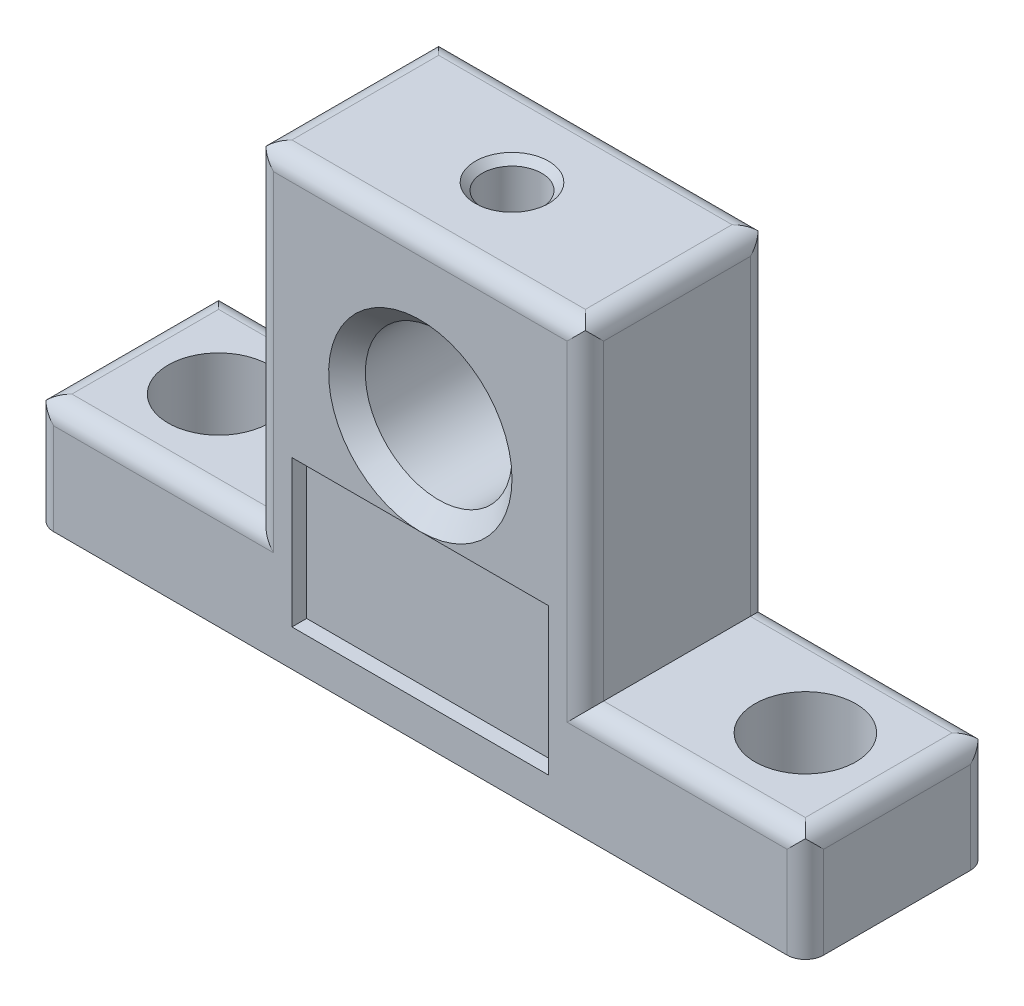
SolidWorks part; units mm, degrees
ref_plane "Front Plane" through (0, 0, 0) normal (0, 0, 1) x (1, 0, 0)
ref_plane "Top Plane" through (0, 0, 0) normal (0, 1, 0) x (1, 0, 0)
ref_plane "Right Plane" through (0, 0, 0) normal (1, 0, 0) x (0, 0, -1)
ref_plane "Plane1" through (0, 0, 0) normal (0, 0, 1) x (1, 0, 0)
sketch "Sketch1" plane through (0, 0, 0) normal (0, 0, 1) x (1, 0, 0)
  line L0 (-21, 0) -> (21, 0)
  line L1 (21, 0) -> (21, 5)
  line L2 (20, 6) -> (-20, 6)
  line L3 (-21, 5) -> (-21, 0)
  arc A0 (21, 5) -> (20, 6) centre (20, 5) ccw
  arc A1 (-20, 6) -> (-21, 5) centre (-20, 5) ccw
extrude "Boss-Extrude1" add sketch "Sketch1" against normal blind 5 and the other way blind 5
ref_plane "Plane2" through (0, 0, 0) normal (1, 0, 0) x (0, 0, -1)
sketch "Sketch2" plane through (0, 0, 0) normal (1, 0, 0) x (0, 0, -1)
  line L0 (-10, -5) -> (10, -5)
  line L1 (10, -5) -> (10, 11)
  line L2 (10, 11) -> (-10, 11)
  line L3 (-10, 11) -> (-10, -5)
  line L4 (-5, 0) -> (5, 0)
  line L5 (5, 0) -> (5, 5)
  line L6 (4, 6) -> (-4, 6)
  line L7 (-5, 5) -> (-5, 0)
  arc A0 (5, 5) -> (4, 6) centre (4, 5) ccw
  arc A1 (-4, 6) -> (-5, 5) centre (-4, 5) ccw
extrude "Cut-Extrude1" cut sketch "Sketch2" against normal blind 42 and the other way blind 42
ref_plane "Plane3" through (0, 0, 0) normal (0, 1, 0) x (1, 0, 0)
sketch "Sketch3" plane through (0, 0, 0) normal (0, 1, 0) x (1, 0, 0)
  line L0 (-31.5, -10) -> (31.5, -10)
  line L1 (31.5, -10) -> (31.5, 10)
  line L2 (31.5, 10) -> (-31.5, 10)
  line L3 (-31.5, 10) -> (-31.5, -10)
  line L4 (-21, 4) -> (-21, -4)
  line L5 (-20, -5) -> (20, -5)
  line L6 (21, -4) -> (21, 4)
  line L7 (20, 5) -> (-20, 5)
  arc A0 (-21, -4) -> (-20, -5) centre (-20, -4) ccw
  arc A1 (20, -5) -> (21, -4) centre (20, -4) ccw
  arc A2 (21, 4) -> (20, 5) centre (20, 4) ccw
  arc A3 (-20, 5) -> (-21, 4) centre (-20, 4) ccw
extrude "Cut-Extrude2" cut sketch "Sketch3" against normal blind 42 and the other way blind 42
ref_plane "Plane4" through (0, 0, 0) normal (0, 1, 0) x (1, 0, 0)
sketch "Sketch4" plane through (0, 0, 0) normal (0, 1, 0) x (1, 0, 0)
  line L0 (-9, 4) -> (-9, -4)
  line L1 (-8, -5) -> (8, -5)
  line L2 (9, -4) -> (9, 4)
  line L3 (8, 5) -> (-8, 5)
  arc A0 (-9, -4) -> (-8, -5) centre (-8, -4) ccw
  arc A1 (8, -5) -> (9, -4) centre (8, -4) ccw
  arc A2 (9, 4) -> (8, 5) centre (8, 4) ccw
  arc A3 (-8, 5) -> (-9, 4) centre (-8, 4) ccw
extrude "Boss-Extrude2" add sketch "Sketch4" along normal blind 24
ref_plane "Plane5" through (0, 0, 0) normal (0, 0, 1) x (1, 0, 0)
sketch "Sketch5" plane through (0, 0, 0) normal (0, 0, 1) x (1, 0, 0)
  line L0 (-9, 48) -> (-9, 23)
  line L1 (-8, 24) -> (8, 24)
  line L2 (9, 23) -> (9, 48)
  line L3 (9, 48) -> (-9, 48)
  arc A0 (-9, 23) -> (-8, 24) centre (-8, 23) cw
  arc A1 (8, 24) -> (9, 23) centre (8, 23) cw
extrude "Cut-Extrude3" cut sketch "Sketch5" against normal blind 10 and the other way blind 10
ref_plane "Plane6" through (0, 0, 0) normal (1, 0, 0) x (0, 0, -1)
sketch "Sketch6" plane through (0, 0, 0) normal (1, 0, 0) x (0, 0, -1)
  line L0 (-5, 48) -> (-5, 23)
  line L1 (-4, 24) -> (4, 24)
  line L2 (5, 23) -> (5, 48)
  line L3 (5, 48) -> (-5, 48)
  arc A0 (-5, 23) -> (-4, 24) centre (-4, 23) cw
  arc A1 (4, 24) -> (5, 23) centre (4, 23) cw
extrude "Cut-Extrude4" cut sketch "Sketch6" against normal blind 18 and the other way blind 18
ref_plane "Plane7" through (0, 0, 0) normal (1, 0, 0) x (0, 0, -1)
sketch "Sketch7" plane through (0, 0, 0) normal (1, 0, 0) x (0, 0, -1)
  line L0 (-5, 15) -> (-5, 20)
  line L1 (-5, 20) -> (-4, 19)
  line L2 (-4, 19) -> (4, 19)
  line L3 (4, 19) -> (5, 20)
  line L4 (5, 20) -> (5, 15)
  line L5 (5, 15) -> (-5, 15)
  line L6 (5, 15) -> (-5, 15) construction
revolve "Cut-Revolve1" cut sketch "Sketch7" angle 360 about L6 reverse direction yes
ref_plane "Plane8" through (0, 0, 0) normal (0, 0, 1) x (1, 0, 0)
sketch "Sketch8" plane through (0, 0, 0) normal (0, 0, 1) x (1, 0, 0)
  line L0 (-16, 0) -> (-18.75, 0)
  line L1 (-18.75, 0) -> (-18.75, 6)
  line L2 (-18.75, 6) -> (-16, 6)
  line L3 (-16, 6) -> (-16, 0)
  line L4 (-16, 6) -> (-16, 0) construction
  dimension "D1" = 2.75
revolve "Cut-Revolve2" cut sketch "Sketch8" angle 360 about L4 reverse direction yes
ref_plane "Plane9" through (0, 0, 0) normal (0, 0, 1) x (1, 0, 0)
sketch "Sketch9" plane through (0, 0, 0) normal (0, 0, 1) x (1, 0, 0)
  line L0 (16, 0) -> (13.25, 0)
  line L1 (13.25, 0) -> (13.25, 6)
  line L2 (13.25, 6) -> (16, 6)
  line L3 (16, 6) -> (16, 0)
  line L4 (16, 6) -> (16, 0) construction
revolve "Cut-Revolve3" cut sketch "Sketch9" angle 360 about L4 reverse direction yes
ref_plane "Plane10" through (0, 0, 0) normal (0, 0, 1) x (1, 0, 0)
sketch "Sketch10" plane through (0, 0, 0) normal (0, 0, 1) x (1, 0, 0)
  line L0 (0, 24) -> (2, 24)
  line L1 (2, 24) -> (1.621, 23.621)
  line L2 (1.621, 23.621) -> (1.621, 19)
  line L3 (1.621, 19) -> (2, 18.621)
  line L4 (2, 18.621) -> (2, 15)
  line L5 (2, 15) -> (0, 15)
  line L6 (0, 15) -> (0, 24)
  line L7 (0, 15) -> (0, 24) construction
revolve "Cut-Revolve4" cut sketch "Sketch10" angle 360 about L7 reverse direction yes
ref_plane "Plane11" through (0, 0, 5) normal (0, 0, 1) x (1, 0, 0)
sketch "Sketch11" plane through (0, 0, 5) normal (0, 0, 1) x (1, 0, 0)
  line L0 (-7, 2) -> (7, 2)
  line L1 (7, 2) -> (7, 10)
  line L2 (7, 10) -> (-7, 10)
  line L3 (-7, 10) -> (-7, 2)
extrude "Cut-Extrude5" cut sketch "Sketch11" against normal blind 0.8
